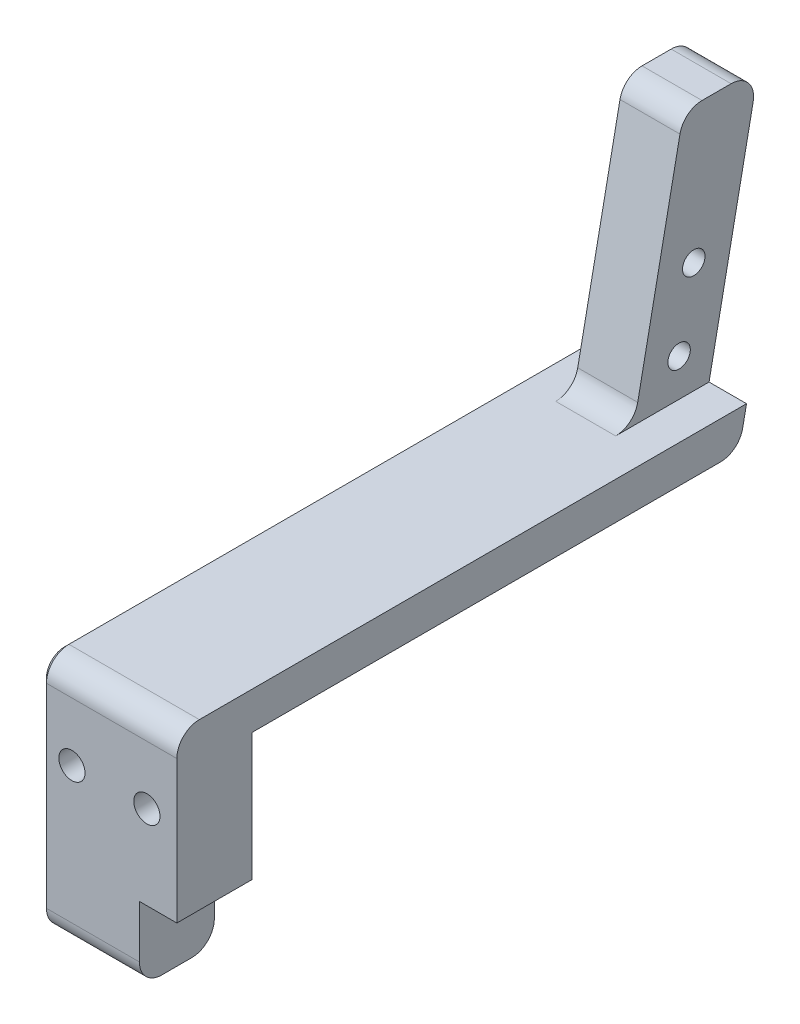
SolidWorks part; units mm, degrees
material "ﾎﾟﾘｴｽﾃﾙ樹脂"
ref_plane "正面" through (0, 0, 0) normal (0, 0, 1) x (1, 0, 0)
ref_plane "平面" through (0, 0, 0) normal (0, 1, 0) x (1, 0, 0)
ref_plane "右側面" through (0, 0, 0) normal (1, 0, 0) x (0, 0, -1)
sketch "ｽｹｯﾁ1" plane through (0, 0, 0) normal (1, 0, 0) x (0, 0, -1)
  line L0 (5, 6.5) -> (-5, 6.5)
  line L1 (-5, -6.5) -> (5, -6.5)
  line L2 (-5, -6.5) -> (-5, 6.5)
  line L3 (-5, 6.5) -> (5, 6.5)
  line L4 (5, -6.5) -> (5, 6.5)
  line L5 (-5, -6.5) -> (5, 6.5) construction
  line L6 (-5, 6.5) -> (5, -6.5) construction
  line L7 (-5, 6.5) -> (3.2581, 47.79)
  line L8 (3.2581, 47.79) -> (13.2581, 47.79)
  line L9 (13.2581, 47.79) -> (5, 6.5)
  point P0 (0, 0)
  dimension "D1" = 13
  dimension "D4" = 101.31
  dimension "D5" = 41.29
  dimension "D6" = 10
extrude "ﾎﾞｽ - 押し出し1" add sketch "ｽｹｯﾁ1" along normal mid plane 18
sketch "ｽｹｯﾁ2" plane through (9, 0, 0) normal (1, 0, 0) x (0, 0, -1)
  line L0 (3.2581, 47.79) -> (-1.1068, 25.966)
  line L1 (-5, 6.5) -> (3.2581, 47.79) construction
  line L2 (-1.1068, 25.966) -> (8.5086, 24.0429)
  line L3 (13.2581, 47.79) -> (5, 6.5) construction
  line L4 (8.5086, 24.0429) -> (13.2581, 47.79)
  line L5 (3.2581, 47.79) -> (13.2581, 47.79) construction
  line L6 (13.2581, 47.79) -> (3.2581, 47.79)
  dimension "D1" = 21.824
extrude "ｶｯﾄ - 押し出し1" cut sketch "ｽｹｯﾁ2" against normal blind 5
mirror "ﾐﾗｰ1" about plane through (0, 0, 0) normal (1, 0, 0) of "ｶｯﾄ - 押し出し1"
sketch "ｽｹｯﾁ3" plane through (0, 0, -5) normal (0, 0, -1) x (-1, 0, 0)
  line L0 (0, 0) -> (0, 50000) construction
  line L2 (-9, -1.5) -> (9, -1.5) construction
  line L5 (-9, -6.5) -> (9, -6.5) construction
  circle A3 centre (5, -1.5) radius 1.75
  circle A4 centre (-5, -1.5) radius 1.75
  dimension "D1" = 10
  dimension "D6" = 3.5
  dimension "D7" = 5
extrude "ｶｯﾄ - 押し出し2" cut sketch "ｽｹｯﾁ3" against normal through all
sketch "ｽｹｯﾁ4" plane through (0, 1.2115, 6.0577) normal (0, 0.1961, 0.9806) x (1, 0, 0)
  line L0 (9, 15.3189) -> (7.5, 15.3189) construction
  line L1 (9, 5.3932) -> (9, 25.2447) construction
  line L2 (0, 47.5009) -> (0, -7.3544) construction
  line L3 (6, 5.3932) -> (9, 5.3932)
  line L4 (6, 5.3932) -> (6, 25.2447)
  line L5 (6, 25.2447) -> (9, 25.2447)
  line L6 (9, 5.3932) -> (9, 25.2447)
  line L7 (6, 5.3932) -> (9, 25.2447) construction
  line L8 (6, 25.2447) -> (9, 5.3932) construction
  line L9 (4, 47.5009) -> (-4, 47.5009) construction
  line L10 (9, -7.3544) -> (-9, -7.3544) construction
  line L11 (-6, 25.2447) -> (-9, 5.3932) construction
  line L12 (-6, 5.3932) -> (-9, 25.2447) construction
  line L13 (-9, 15.3189) -> (-7.5, 15.3189) construction
  line L14 (-9, 5.3932) -> (-9, 25.2447)
  line L15 (-6, 25.2447) -> (-9, 25.2447)
  line L16 (-6, 5.3932) -> (-6, 25.2447)
  line L17 (-6, 5.3932) -> (-9, 5.3932)
  dimension "D1" = 3
extrude "ﾎﾞｽ - 押し出し2" add sketch "ｽｹｯﾁ4" along normal blind 5.5
fillet "ﾌｨﾚｯﾄ2" radius 5 2 edges at (0, 47.79, -13.2581) (0, 47.79, -3.2581)
fillet "ﾌｨﾚｯﾄ3" radius 5 2 edges at (-4, 25.0045, -3.7009) (4, 25.0045, -3.7009)
chamfer "面取り2" distance 1 angle 45 1 edges at (9, 25.5438, -1.0043)
sketch "ｽｹｯﾁ6" plane through (0, -6.5, 0) normal (0, -1, 0) x (1, 0, 0)
  line L1 (-9, -5) -> (9, -5)
  line L2 (-9, -5) -> (-9, 5)
  line L3 (-9, 5) -> (9, 5)
  line L4 (9, -5) -> (9, 5)
  line L5 (-9, -5) -> (9, 5) construction
  line L6 (-9, 5) -> (9, -5) construction
  point P0 (0, 0)
extrude "ﾎﾞｽ - 押し出し3" add sketch "ｽｹｯﾁ6" along normal blind 16.2
sketch "ｽｹｯﾁ7" plane through (0, 0, 5) normal (0, 0, 1) x (1, 0, 0)
  line L1 (9, -22.7) -> (4, -22.7)
  line L2 (9, -22.7) -> (9, -12.7)
  line L3 (9, -12.7) -> (4, -12.7)
  line L4 (4, -22.7) -> (4, -12.7)
  dimension "D1" = 5
  dimension "D2" = 10
extrude "ｶｯﾄ - 押し出し5" cut sketch "ｽｹｯﾁ7" against normal through all
sketch "ｽｹｯﾁ8" plane through (9, 0, 0) normal (1, 0, 0) x (0, 0, -1)
  line L1 (-14.7304, 6.5) -> (15.2696, 6.5)
  line L2 (-14.7304, 6.5) -> (-14.7304, 56.5)
  line L3 (-14.7304, 56.5) -> (15.2696, 56.5)
  line L4 (15.2696, 6.5) -> (15.2696, 56.5)
  line L5 (-14.7304, 6.5) -> (15.2696, 6.5)
  line L6 (-14.7304, 6.5) -> (-14.7304, 1.5)
  line L7 (-14.7304, 1.5) -> (15.2696, 1.5)
  line L8 (15.2696, 6.5) -> (15.2696, 1.5)
  point P0 (-5, 6.5)
  point P1 (5, 6.5)
  line M7 (5, 6.5) -> (8.3125, 23.0623)
  line M8 (8.3125, 23.0623) -> (-6.6961, 26.0641)
  line M9 (-6.6961, 26.0641) -> (-10.3932, 7.5786)
  line M10 (-10.3932, 7.5786) -> (-5, 6.5)
  dimension "D1" = 30
  dimension "D2" = 50
  dimension "D3" = 5
extrude "ｶｯﾄ - 押し出し6" cut sketch "ｽｹｯﾁ8" against normal through all contours L1 L4 L3 L2 M10 M9 M8 M7 | L1 M10 M7 M8 M9
sketch "ｽｹｯﾁ10" plane through (9, 0, 0) normal (1, 0, 0) x (0, 0, -1)
  line L1 (-5, 9.3) -> (61, 9.3)
  line L2 (61, 9.3) -> (67.6, 42.3)
  line L3 (67.6, 42.3) -> (77.6, 42.3)
  line L4 (77.6, 42.3) -> (70, 4.3)
  line L6 (-5, -12.7) -> (-5, 6.5) construction
  line L8 (5, -22.7) -> (-5, -22.7) construction
  line L9 (5, -12.7) -> (5, 6.5) construction
  line L10 (70, 4.3) -> (5, 4.3)
  line L13 (-5, 9.3) -> (-5, 6.5)
  line M6 (5, -12.7) -> (5, 6.5)
  dimension "D1" = 32
  dimension "D2" = 5
  dimension "D3" = 75
  dimension "D4" = 10
  dimension "D5" = 101.31
  dimension "D6" = 33
extrude "ﾎﾞｽ - 押し出し4" add sketch "ｽｹｯﾁ10" against normal up to surface (18 mm away) contours L10 L4 L3 L2 L1 M6 up to face at (-9, -8.1, 0)
sketch "ｽｹｯﾁ11" plane through (0, 42.3, 0) normal (0, 1, 0) x (1, 0, 0)
  line L0 (0, 77.6) -> (0, 0) construction
  line L1 (-9, 77.6) -> (9, 77.6) construction
  line L4 (-4, 59) -> (4, 59)
  line L5 (-4, 59) -> (-4, 77.6)
  line L6 (-4, 77.6) -> (4, 77.6)
  line L7 (4, 59) -> (4, 77.6)
  line L8 (-4, 59) -> (4, 77.6) construction
  line L9 (-4, 77.6) -> (4, 59) construction
  line L10 (4, 77.6) -> (9, 77.6)
  line L11 (9, 77.6) -> (9, 59)
  line L12 (9, 59) -> (4, 59)
  line L13 (-4, 59) -> (-9, 59)
  line L14 (-9, 59) -> (-9, 77.6)
  line L15 (-9, 77.6) -> (-4, 77.6)
  line L17 (-9, 61) -> (9, 61) construction
  point P6 (0, 68.3)
  dimension "D1" = 8
  dimension "D2" = 2
extrude "ｶｯﾄ - 押し出し7" cut sketch "ｽｹｯﾁ11" against normal up to surface (33 mm away)
sketch "ｽｹｯﾁ12" plane through (4, 0, 0) normal (1, 0, 0) x (0, 0, -1)
  line L0 (72.6, 42.3) -> (66, 9.3) construction
  line L1 (67.6, 42.3) -> (77.6, 42.3) construction
  line L2 (71, 9.3) -> (61, 9.3) construction
  line L3 (61, 9.3) -> (71, 9.3) construction
  circle A0 centre (68.9612, 24.1058) radius 1.5
  circle A1 centre (67, 14.3) radius 1.5
  dimension "D1" = 10
  dimension "D2" = 5
  dimension "D3" = 3
extrude "ｶｯﾄ - 押し出し8" cut sketch "ｽｹｯﾁ12" against normal through all
fillet "ﾌｨﾚｯﾄ4" radius 3 7 edges at (-2.5, -22.7, 5) (-2.5, -22.7, -5) (0, 4.3, -70) (0, 42.3, -77.6) (0, 42.3, -67.6) (0, 9.3, -61) (0, 9.3, 5)
chamfer "面取り3" distance 0.6 angle 45 10 edges at (-9, -21.8213, -4.1213) (-9, -7.7, -5) (-9, 4.3, -36.2703) (-9, 4.98, -69.4426) (-9, 8.0058, -70.7412) (-9, 9.3, -34.5) (-9, 8.4213, 4.1213) (-9, -6.7, 5) (-9, -21.8213, 4.1213) (-9, -22.7, 0)
